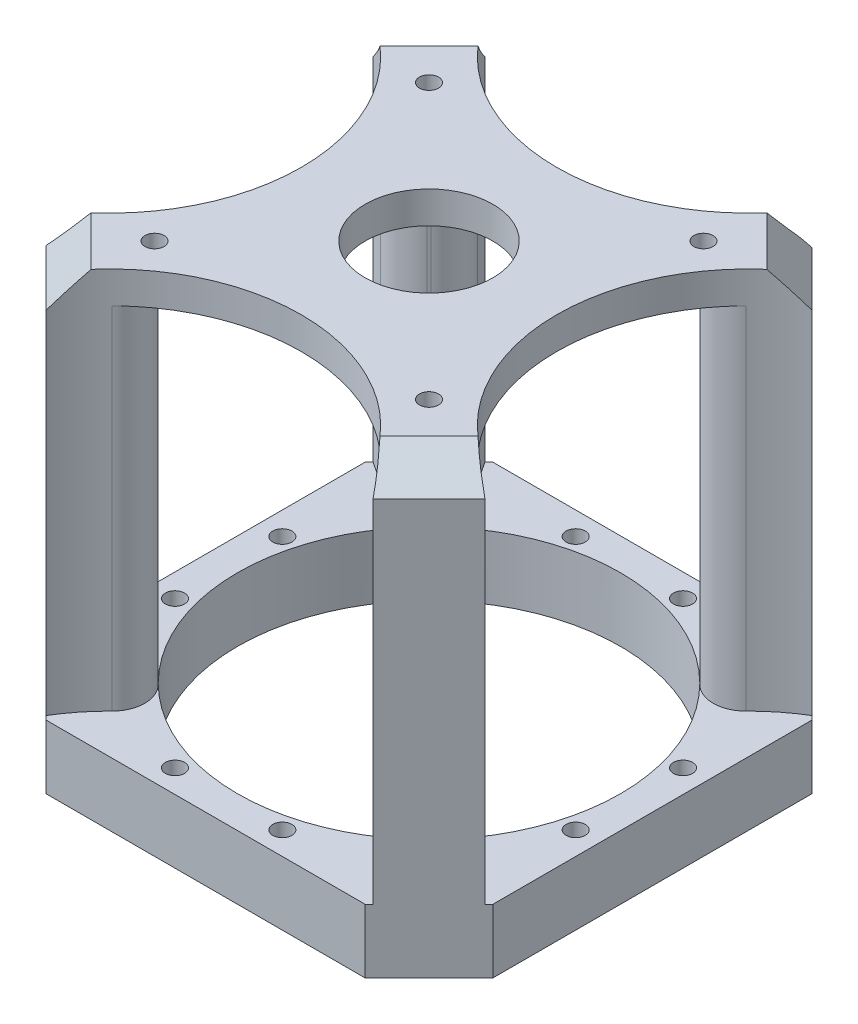
SolidWorks part; units mm, degrees
ref_plane "Front Plane" through (0, 0, 0) normal (0, 0, 1) x (1, 0, 0)
ref_plane "Top Plane" through (0, 0, 0) normal (0, 1, 0) x (1, 0, 0)
ref_plane "Right Plane" through (0, 0, 0) normal (1, 0, 0) x (0, 0, -1)
sketch "Sketch1" plane through (0, 0, 0) normal (0, 1, 0) x (1, 0, 0)
  line L0 (-8.4116, 31.3926) -> (0, 0) construction
  line L1 (-35, -35) -> (35, -35)
  line L2 (-35, -35) -> (-35, 35)
  line L3 (-35, 35) -> (35, 35)
  line L4 (35, -35) -> (35, 35)
  line L5 (-35, -35) -> (35, 35) construction
  line L6 (-35, 35) -> (35, -35) construction
  line L7 (0, 0) -> (8.6813, 0) construction
  circle A0 centre (0, 0) radius 35 construction
  circle A1 centre (0, 0) radius 30
  circle A2 centre (0, 0) radius 32.5 construction
  circle A3 centre (-8.4116, 31.3926) radius 1.5
  circle A4 centre (8.4116, 31.3926) radius 1.5
  circle A6 centre (31.3926, 8.4116) radius 1.5
  circle A7 centre (31.3926, -8.4116) radius 1.5
  circle A9 centre (8.4116, -31.3926) radius 1.5
  circle A10 centre (-8.4116, -31.3926) radius 1.5
  circle A12 centre (-31.3926, -8.4116) radius 1.5
  circle A13 centre (-31.3926, 8.4116) radius 1.5
  circle A15 centre (22.981, -22.981) radius 1.5 [skipped]
  circle A16 centre (22.981, 22.981) radius 1.5 [skipped]
  circle A17 centre (-22.981, 22.981) radius 1.5 [skipped]
  circle A18 centre (-22.981, -22.981) radius 1.5 [skipped]
  point P35 (0, 0)
  dimension "D1" = 70
  dimension "D2" = 60
  dimension "D3" = 65
  dimension "D4" = 3
  dimension "D6" = 105
  dimension "D5" = 12
extrude "Boss-Extrude1" add sketch "Sketch1" along normal blind 65
sketch "Sketch2" plane through (0, 65, 0) normal (0, 1, 0) x (1, 0, 0)
  line L1 (-35, -35) -> (35, -35)
  line L2 (-35, -35) -> (-35, 35)
  line L3 (-35, 35) -> (35, 35)
  line L4 (35, -35) -> (35, 35)
  line L5 (-35, -35) -> (35, 35) construction
  line L6 (-35, 35) -> (35, -35) construction
  line L7 (-21.5, -21.5) -> (21.5, -21.5) construction
  line L8 (-21.5, -21.5) -> (-21.5, 21.5) construction
  line L9 (-21.5, 21.5) -> (21.5, 21.5) construction
  line L10 (21.5, -21.5) -> (21.5, 21.5) construction
  line L11 (-21.5, -21.5) -> (21.5, 21.5) construction
  line L12 (-21.5, 21.5) -> (21.5, -21.5) construction
  circle A0 centre (0, 0) radius 32.5 construction
  circle A1 centre (0, 32.5) radius 1.5
  circle A2 centre (16.25, 28.1458) radius 1.5
  circle A3 centre (28.1458, 16.25) radius 1.5
  circle A4 centre (32.5, 0) radius 1.5
  circle A5 centre (28.1458, -16.25) radius 1.5
  circle A6 centre (16.25, -28.1458) radius 1.5
  circle A7 centre (0, -32.5) radius 1.5
  circle A8 centre (-16.25, -28.1458) radius 1.5
  circle A9 centre (-28.1458, -16.25) radius 1.5
  circle A10 centre (-32.5, 0) radius 1.5
  circle A11 centre (-28.1458, 16.25) radius 1.5
  circle A12 centre (-16.25, 28.1458) radius 1.5
  circle A13 centre (0, 0) radius 10
  circle A14 centre (-21.5, 21.5) radius 1.5
  circle A15 centre (21.5, 21.5) radius 1.5
  circle A16 centre (21.5, -21.5) radius 1.5
  circle A17 centre (-21.5, -21.5) radius 1.5
  point P0 (0, 0)
  point P37 (0, 0)
  dimension "D1" = 65
  dimension "D3" = 20
  dimension "D4" = 43
  dimension "D2" = 12
extrude "Boss-Extrude2" add sketch "Sketch2" along normal blind 5
sketch "Sketch3" plane through (0, 70, 0) normal (0, 1, 0) x (1, 0, 0)
  line L0 (0, 0) -> (0, 50) construction
  circle A0 centre (0, 50) radius 30
  dimension "D2" = 60
  dimension "D1" = 50
extrude "Cut-Extrude1" cut sketch "Sketch3" against normal blind 60
pattern_circular "CirPattern1" count 4 over 360 about axis through (0, 65, 0) along (0, -1, 0) of "Cut-Extrude1" reverse direction yes
fillet "Fillet2" radius 5.1 9 edges at (25, 37.5, 16.5831) (25, 37.5, -16.5831) (-16.5831, 37.5, 25) (16.5831, 37.5, 25) (25.9808, 40, -35) (-25, 37.5, -16.5831) (-25, 37.5, 16.5831) (-16.5831, 37.5, -25) (16.5831, 37.5, -25)
chamfer "Chamfer1" distance 10 angle 45 4 edges at (35, 35, 35) (35, 35, -35) (-35, 35, -35) (-35, 35, 35)
chamfer "Chamfer2" distance 5 angle 45 4 edges at (-30, 70, 30) (30, 70, 30) (30.1385, 70, -29.8615) (-30, 70, -30)
